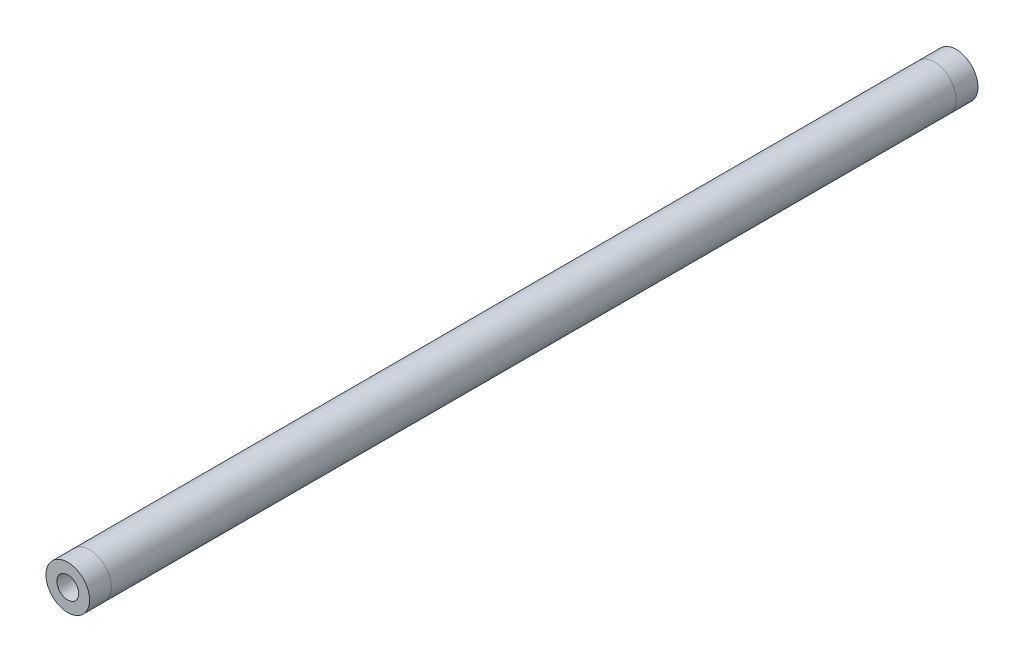
SolidWorks part; units mm, degrees
ref_plane "Front Plane" through (0, 0, 0) normal (0, 0, 1) x (1, 0, 0)
ref_plane "Top Plane" through (0, 0, 0) normal (0, 1, 0) x (1, 0, 0)
ref_plane "Right Plane" through (0, 0, 0) normal (1, 0, 0) x (0, 0, -1)
sketch "Axis" plane through (0, 0, 0) normal (1, 0, 0) x (0, 0, -1)
  line L0 (0, 0) -> (258.6114, 0) construction
  line L1 (258.6114, 0) -> (252.2614, 0)
  line L2 (258.6114, 0) -> (280.5062, 0) construction
  line L3 (0, 0) -> (-21.8948, 0) construction
  point P4 (0, 0)
  point P5 (258.6114, 0)
  point P6 (252.2614, 0)
  dimension "D1" = 6.35
  dimension "D2" = 21.8948
  dimension "D3" = 21.8948
sketch "Sketch1" plane through (0, 0, 0) normal (0, 0, 1) x (1, 0, 0)
  circle A0 centre (0, 0) radius 6.35
  circle A1 centre (0, 0) radius 4.826
  circle A2 centre (0, 0) radius 3.175
  dimension "D1" = 12.7
  dimension "D2" = 1.524
  dimension "D3" = 6.35
extrude "Threaded insert 1-1" add sketch "Sketch1" against normal blind 6.35 contours A0 A1 | A1 A2 region at (-6.1704, 0, 0) region at (-4.6895, 0, 0)
extrude "Threaded insert 1-2" add sketch "Sketch1<3>" against normal blind 9.525 from surface contours A1 A2 region at (-4.6895, 0, 0) starting at face at (6.35, 0, -6.35)
sketch "Sketch1<3>" plane through (0, 0, 0) normal (0, 0, 1) x (1, 0, 0) same geometry as "Sketch1"
extrude "Tube extrude" add sketch "Sketch1<4>" against normal up to vertex (252.2614 mm away) from surface separate body contours A0 A1 region at (-6.1704, 0, 0) up to point (0, 0, -252.2614) starting at face at (4.826, 0, -6.35)
sketch "Sketch1<4>" plane through (0, 0, 0) normal (0, 0, 1) x (1, 0, 0) same geometry as "Sketch1"
extrude "Threaded insert 2-1" add sketch "Sketch1<6>" along normal blind 9.525 from surface separate body contours A1 A2 region at (-4.6895, 0, 0) starting at face at (4.826, 0, -252.2614)
sketch "Sketch1<6>" plane through (0, 0, 0) normal (0, 0, 1) x (1, 0, 0) same geometry as "Sketch1"
extrude "Threaded insert 2-2" add sketch "Sketch1<9>" against normal blind 6.35 from surface separate body contours A1 A2 | A0 A1 region at (-6.1704, 0, 0) region at (-4.6895, 0, 0) starting at face at (4.826, 0, -252.2614)
sketch "Sketch1<9>" plane through (0, 0, 0) normal (0, 0, 1) x (1, 0, 0) same geometry as "Sketch1"
combine bodies "Combine1" operation type add bodies to combine 106 104
equation "\"Threaded insert outer thickness\"= .25"
equation "\"D1@Threaded insert 1-1\"=\"Threaded insert outer thickness\""
equation "\"D1@Threaded insert 2-2\"=\"Threaded insert outer thickness\""
equation "\"D1@Axis\" = \"Threaded insert outer thickness\""
